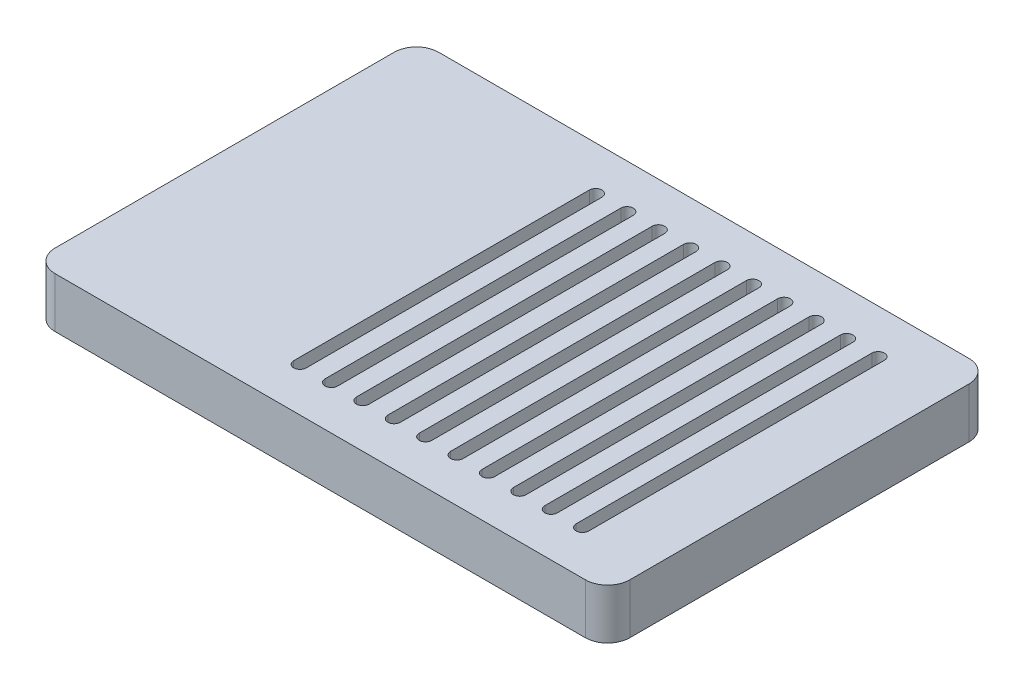
SolidWorks part; units mm, degrees
ref_plane "Спереди" through (0, 0, 0) normal (0, 0, 1) x (1, 0, 0)
ref_plane "Сверху" through (0, 0, 0) normal (0, 1, 0) x (1, 0, 0)
ref_plane "Справа" through (0, 0, 0) normal (1, 0, 0) x (0, 0, -1)
ref_plane "Plane1" through (0, 22.1, 0) normal (0, 1, 0) x (1, 0, 0)
sketch "Sketch1" plane through (0, 22.1, -139.3737) normal (0, 1, 0) x (1, 0, 0)
  line L0 (46.5, -162.24) -> (46.5, -101.14)
  line L1 (46.5, -101.14) -> (-45.05, -101.14)
  line L2 (-45.05, -101.14) -> (-45.05, -162.24)
  line L3 (-45.05, -162.24) -> (46.5, -162.24)
extrude "Boss-Extrude1" add sketch "Sketch1" against normal blind 8
sketch "Sketch2" plane through (0, 14.1, -139.3737) normal (0, -1, 0) x (1, 0, 0)
  line L0 (-44.05, 161.24) -> (-44.05, 102.14)
  line L1 (-44.05, 102.14) -> (45.5, 102.14)
  line L2 (45.5, 102.14) -> (45.5, 161.24)
  line L3 (45.5, 161.24) -> (-44.05, 161.24)
  line L4 (-45.05, 162.24) -> (46.5, 162.24) construction
  line L5 (-45.05, 101.14) -> (-45.05, 162.24) construction
  line L6 (46.5, 101.14) -> (-45.05, 101.14) construction
  line L7 (46.5, 162.24) -> (46.5, 101.14) construction
  dimension "D1" = 1
  dimension "D2" = 1
  dimension "D3" = 1
  dimension "D4" = 1
extrude "Cut-Extrude1" cut sketch "Sketch2" against normal blind 6
sketch "Sketch3" plane through (-45.05, 0, -139.3737) normal (-1, 0, 0) x (0, 0, 1)
  line L0 (157.5557, 14.1) -> (157.5557, 19.25)
  line L1 (157.5557, 19.25) -> (143.8557, 19.25)
  line L2 (143.8557, 19.25) -> (143.8557, 14.1)
  line L3 (143.8557, 14.1) -> (157.5557, 14.1)
extrude "Cut-Extrude2" cut sketch "Sketch3" against normal up to next
sketch "Sketch4" plane through (-45.05, 0, -139.3737) normal (-1, 0, 0) x (0, 0, 1)
  line L0 (139.1557, 14.1) -> (139.1557, 19.25)
  line L1 (139.1557, 19.25) -> (125.4557, 19.25)
  line L2 (125.4557, 19.25) -> (125.4557, 14.1)
  line L3 (125.4557, 14.1) -> (139.1557, 14.1)
extrude "Cut-Extrude3" cut sketch "Sketch4" against normal up to next
sketch "Sketch5" plane through (-45.05, 0, -139.3737) normal (-1, 0, 0) x (0, 0, 1)
  line L0 (106.7182, 14.1) -> (120.8912, 14.1)
  line L1 (118.9547, 15.6) -> (108.6547, 15.6)
  arc A0 (120.8912, 14.1) -> (118.9547, 15.6) centre (118.9547, 13.6) ccw
  arc A1 (108.6547, 15.6) -> (106.7182, 14.1) centre (108.6547, 13.6) ccw
extrude "Cut-Extrude4" cut sketch "Sketch5" against normal up to next
fillet "Fillet1" radius 2 8 edges at (-44.55, 19.25, 18.182) (-44.55, 19.25, 4.482) (45.5, 17.1, -37.2337) (45.5, 17.1, 21.8663) (-44.55, 19.25, -13.918) (-44.05, 17.1, -37.2337) (-44.55, 19.25, -0.218) (-44.05, 17.1, 21.8663) tangent propagation no
fillet "Fillet2" radius 3.55 4 edges at (46.5, 18.1, -38.2337) (46.5, 18.1, 22.8663) (-45.05, 18.1, 22.8663) (-45.05, 18.1, -38.2337) tangent propagation no
sketch "Sketch6" plane through (0, 22.1, 0) normal (0, 1, 0) x (1, 0, 0)
  line L0 (35.5, 31.2337) -> (35.5, -15.8663) construction
  line L1 (36.5, 31.2337) -> (36.5, -15.8663)
  line L2 (34.5, 31.2337) -> (34.5, -15.8663)
  line L3 (-41.5, -22.8663) -> (42.95, -22.8663) construction
  line L4 (42.95, 38.2337) -> (-41.5, 38.2337) construction
  line L5 (46.5, -19.3163) -> (46.5, 34.6837) construction
  arc A0 (36.5, 31.2337) -> (34.5, 31.2337) centre (35.5, 31.2337) ccw
  arc A1 (34.5, -15.8663) -> (36.5, -15.8663) centre (35.5, -15.8663) ccw
  point P2 (35.5, 7.6837)
  dimension "D1" = 7
  dimension "D2" = 7
  dimension "D3" = 10
  dimension "D4" = 2
extrude "Cut-Extrude5" cut sketch "Sketch6" against normal up to surface (2 mm away) up to face at (0.725, 20.1, -7.6837)
pattern_linear "LPattern1" count 10 spacing 5 along (-1, 0, 0) of "Cut-Extrude5"
